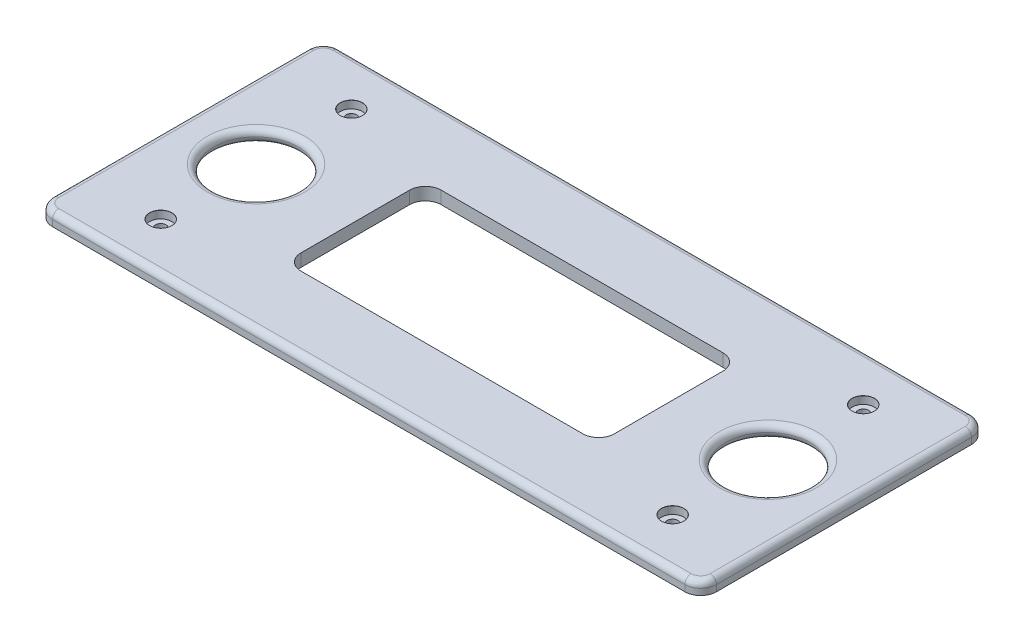
SolidWorks part; units mm, degrees
ref_plane "Front Plane" through (0, 0, 0) normal (0, 0, 1) x (1, 0, 0)
ref_plane "Top Plane" through (0, 0, 0) normal (0, 1, 0) x (1, 0, 0)
ref_plane "Right Plane" through (0, 0, 0) normal (1, 0, 0) x (0, 0, -1)
sketch "Sketch1" plane through (0, 0, 0) normal (0, 1, 0) x (1, 0, 0)
  line L1 (-105.163, 45.4) -> (105.163, 45.4)
  line L2 (-105.163, 45.4) -> (-105.163, -45.4)
  line L3 (-105.163, -45.4) -> (105.163, -45.4)
  line L4 (105.163, 45.4) -> (105.163, -45.4)
  line L5 (-105.163, 45.4) -> (105.163, -45.4) construction
  line L6 (-105.163, -45.4) -> (105.163, 45.4) construction
  point P0 (0, 0)
  dimension "D1" = 90.8
  dimension "D2" = 210.326
extrude "Boss-Extrude1" add sketch "Sketch1" along normal blind 4
sketch "Sketch3" plane through (0, 4, 0) normal (0, 1, 0) x (1, 0, 0)
  line L0 (-81.0815, 30.1897) -> (81.0815, 30.1897) construction
  line L1 (81.0815, 30.1897) -> (81.0815, -30.1897) construction
  line L2 (81.0815, -30.1897) -> (-81.0815, -30.1897) construction
  line L3 (-81.0815, -30.1897) -> (-81.0815, 30.1897) construction
  line L4 (-105.163, 45.4) -> (-105.163, -45.4) construction
  line L5 (105.163, 45.4) -> (-105.163, 45.4) construction
  point P0 (-81.0815, 30.1897)
  point P1 (81.0815, 30.1897)
  point P2 (-81.0815, -30.1897)
  point P3 (81.0815, -30.1897)
  point P12 (-81.0815, 0)
  point P13 (0, 30.1897)
  dimension "D1" = 24.0815
  dimension "D2" = 15.2103
hole_wizard "CBORE for M3 Pan Head Machine Screw1" positions "Sketch4" profile "Sketch5" counterbore size "M3" standard "ANSI Metric" end condition through all
sketch "Sketch4" plane through (0, 4, 0) normal (0, 1, 0) x (1, 0, 0)
  point P0 (-81.0815, 30.1897)
  point P3 (81.0815, 30.1897)
  point P6 (81.0815, -30.1897)
  point P9 (-81.0815, -30.1897)
sketch "Sketch5" plane through (-81.0815, 4, -30.1897) normal (1, 0, 0) x (0, 0, 1)
  line L0 (0, 0) -> (0, 4)
  line L1 (0, 4) -> (1.7, 4)
  line L3 (1.7, 4) -> (1.7, 2.4)
  line L4 (3.5, 2.4) -> (1.7, 2.4)
  line L5 (3.5, 2.4) -> (3.5, 0.025)
  line L6 (3.5, 0.025) -> (3.525, 0)
  line L7 (3.525, 0) -> (0, 0)
  line L8 (-3.5, 0.025) -> (-3.525, 0) construction
  line L11 (0, -6.35) -> (0, 107.95) construction
  dimension "Thru Hole Dia." = 3.4
  dimension "Thru Hole Depth" = 4
  dimension "C'Bore Dia." = 7
  dimension "C'Bore Depth" = 2.4
  dimension "Near C'Sink Dia." = 7.05
  dimension "Near C'Sink Angle" = 90
sketch "Sketch2" plane through (0, 4, 0) normal (0, 1, 0) x (1, 0, 0)
  line L1 (-49.641, 22.209) -> (49.641, 22.209)
  line L2 (-49.641, 22.209) -> (-49.641, -22.209)
  line L3 (-49.641, -22.209) -> (49.641, -22.209)
  line L4 (49.641, 22.209) -> (49.641, -22.209)
  line L5 (-49.641, 22.209) -> (49.641, -22.209) construction
  line L6 (-49.641, -22.209) -> (49.641, 22.209) construction
  line L7 (-81.0815, 0) -> (81.0815, 0) construction
  line L8 (-81.0815, -30.1897) -> (-81.0815, 30.1897) construction
  circle A0 centre (-81.0815, 0) radius 13.408
  circle A1 centre (81.0815, 0) radius 13.408
  point P0 (0, 0)
  point P9 (0, 0)
  point P13 (0, 0)
  dimension "D3" = 26.816
  dimension "D1" = 44.418
  dimension "D2" = 99.282
extrude "Cut-Extrude1" cut sketch "Sketch2" against normal blind 4
fillet "Fillet1" radius 5 8 edges at (49.641, 2, 22.209) (-49.641, 2, 22.209) (49.641, 2, -22.209) (-49.641, 2, -22.209) (105.163, 2, -45.4) (105.163, 2, 45.4) (-105.163, 2, 45.4) (-105.163, 2, -45.4)
fillet "Fillet2" radius 2 12 edges at (81.0815, 0, 13.408) (-81.0815, 0, 13.408) (81.0815, 4, 13.408) (-81.0815, 4, 13.408) (103.6985, 4, 43.9355) (0, 4, 45.4) (-103.6985, 4, 43.9355) (-105.163, 4, 0) (-103.6985, 4, -43.9355) (0, 4, -45.4) (103.6985, 4, -43.9355) (105.163, 4, 0)
